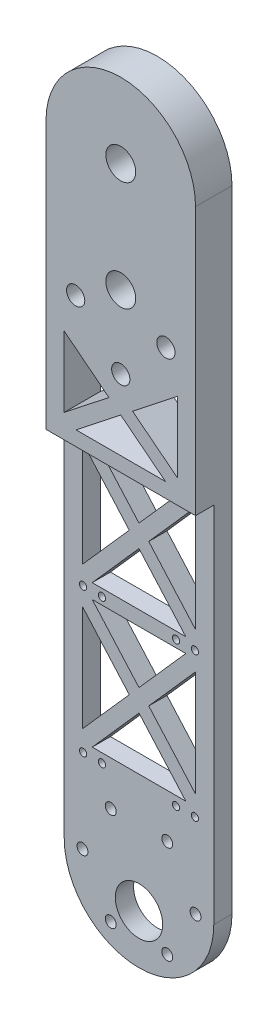
SolidWorks part; units mm, degrees
ref_plane "정면" through (0, 0, 0) normal (0, 0, 1) x (1, 0, 0)
ref_plane "윗면" through (0, 0, 0) normal (0, 1, 0) x (1, 0, 0)
ref_plane "우측면" through (0, 0, 0) normal (1, 0, 0) x (0, 0, -1)
sketch "스케치1" plane through (0, 0, 0) normal (0, 0, 1) x (1, 0, 0)
  line L0 (-20.5, 0) -> (-20.5, 173)
  line L1 (20.5, 0) -> (20.5, 173)
  line L2 (20.5, 173) -> (-20.5, 173) construction
  line L3 (-20.5, 143) -> (20.5, 143) construction
  circle A0 centre (0, 0) radius 20.5
  circle A1 centre (0, 0) radius 15.5 construction
  circle A2 centre (-15.5, 0) radius 1.5
  circle A3 centre (-7.75, 13.4234) radius 1.5
  circle A4 centre (7.75, 13.4234) radius 1.5
  circle A5 centre (15.5, 0) radius 1.5
  circle A6 centre (7.75, -13.4234) radius 1.5
  circle A7 centre (-7.75, -13.4234) radius 1.5
  circle A8 centre (0, -7) radius 6.5
  circle A9 centre (0, 173) radius 20.5
  point P19 (0, 0)
  dimension "D1" = 31
  dimension "D2" = 3
  dimension "D4" = 13
  dimension "D6" = 5
  dimension "D5" = 7
  dimension "D7" = 180
  dimension "D8" = 30
  dimension "D3" = 6
extrude "보스-돌출1" add sketch "스케치1" against normal blind 10 contours A9 L0 A0 L1 | A9 | A0 A8 A7 A6 A5 A4 A3 A2 region at (0, 86.5, 0) region at (0, 0.8114, 0) region at (0, 173, 0)
sketch "스케치2" plane through (0, 0, 0) normal (0, 0, 1) x (1, 0, 0)
  line L0 (-20.5, 143) -> (20.5, 143) construction
  circle A0 centre (0, 173) radius 4.1
  circle A1 centre (0, 143) radius 4.1
  dimension "D1" = 8.2
  dimension "D2" = 8.2
extrude "컷-돌출1" cut sketch "스케치2" against normal blind 10
sketch "스케치3" plane through (0, 0, 0) normal (0, 0, 1) x (1, 0, 0)
  line L0 (-20.5, 133) -> (20.5, 133) construction
  line L1 (-20.5, 0) -> (-20.5, 173) construction
  line L2 (20.5, 0) -> (20.5, 173) construction
  line L3 (-15.5, 128) -> (15.5, 103.625) construction
  line L4 (-20.5, 143) -> (20.5, 143) construction
  line L5 (-20.5, 20.5) -> (20.5, 20.5) construction
  line L6 (-15.5, 128) -> (15.5, 128)
  line L7 (-15.5, 128) -> (-15.5, 25.5)
  line L8 (-15.5, 25.5) -> (15.5, 25.5)
  line L9 (15.5, 128) -> (15.5, 25.5)
  line L10 (-15.5, 125.4558) -> (12.2643, 103.625)
  line L11 (-12.2643, 128) -> (15.5, 106.1692)
  line L12 (15.5, 128) -> (-15.5, 103.625) construction
  line L13 (12.2643, 128) -> (-15.5, 106.1692)
  line L14 (15.5, 125.4558) -> (-12.2643, 103.625)
  line L15 (-15.5, 99.625) -> (15.5, 99.625)
  line L16 (-15.5, 62.56) -> (15.5, 62.56) construction
  line L17 (-15.5, 64.56) -> (15.5, 64.56)
  line L18 (-15.5, 60.56) -> (15.5, 60.56)
  line L19 (-15.5, 99.625) -> (15.5, 64.56) construction
  line L20 (-15.5, 64.56) -> (15.5, 99.625) construction
  line L21 (15.5, 60.56) -> (-15.5, 25.5) construction
  line L22 (-15.5, 60.56) -> (15.5, 25.5) construction
  line L23 (-12.8305, 99.625) -> (15.5, 67.5796)
  line L24 (15.5, 103.625) -> (-15.5, 103.625)
  line L25 (-15.5, 96.6054) -> (12.8305, 64.56)
  line L26 (12.8305, 99.625) -> (-15.5, 67.5796)
  line L27 (15.5, 96.6054) -> (-12.8305, 64.56)
  line L28 (-12.8303, 60.56) -> (15.5, 28.5193)
  line L29 (-15.5, 57.5407) -> (12.8303, 25.5)
  line L30 (12.8303, 60.56) -> (-15.5, 28.5193)
  line L31 (15.5, 57.5407) -> (-12.8303, 25.5)
  circle A0 centre (0, 0) radius 20.5 construction
  point P6 (0, 71.75)
  dimension "D1" = 10
  dimension "D2" = 5
  dimension "D3" = 5
  dimension "D4" = 5
  dimension "D5" = 5
  dimension "D6" = 20.5
  dimension "D7" = 24.375
  dimension "D8" = 2
  dimension "D9" = 2
  dimension "D10" = 2
  dimension "D11" = 2
  dimension "D12" = 4
  dimension "D13" = 37.065
  dimension "D14" = 2
  dimension "D15" = 2
  dimension "D16" = 2
  dimension "D17" = 2
  dimension "D18" = 2
  dimension "D19" = 2
  dimension "D20" = 2
  dimension "D21" = 2
  dimension "D22" = 2
  dimension "D23" = 2
sketch "스케치4" plane through (0, 0, 0) normal (0, 0, 1) x (1, 0, 0)
  line L7 (-20.5, 0) -> (-20.5, 173) construction
  line L8 (20.5, -20.5) -> (-20.5, -20.5)
  line L9 (20.5, -20.5) -> (20.5, 99.625)
  line L10 (20.5, 99.625) -> (-20.5, 99.625)
  line L11 (-20.5, -20.5) -> (-20.5, 99.625)
  line L12 (-15.5, 99.625) -> (15.5, 99.625) construction
  dimension "D1" = 0
extrude "컷-돌출3" cut sketch "스케치4" against normal blind 5
extrude "컷-돌출4" cut sketch "스케치3" against normal blind 10 and the other way through all contours L9 L14 L11 | L24 L10 L14 | L13 L10 L7 region at (-11.4119, 115.8125, 0) region at (11.4119, 115.8125, 0) region at (0, 106.8394, 0)
extrude "컷-돌출5" cut sketch "스케치3<4>" against normal blind 10 and the other way through all contours L26 L15 L23 | L9 L27 L23 | L25 L27 L17 | L26 L25 L7 | L30 L18 L28 | L30 L29 L7 | L29 L31 L8 | L9 L31 L28 region at (-11.2232, 82.0925, 0) region at (0, 94.7874, 0) region at (11.2232, 82.0925, 0) region at (0, 69.3976, 0) region at (-11.2232, 43.03, 0) region at (0, 55.7231, 0) region at (11.2232, 43.03, 0) region at (0, 30.3369, 0)
sketch "스케치3<4>" plane through (0, 0, 0) normal (0, 0, 1) x (1, 0, 0) same geometry as "스케치3"
sketch "스케치5" plane through (0, 0, -5) normal (0, 0, 1) x (1, 0, 0)
  line L0 (-20.5, 99.625) -> (-20.5, 0) construction
  line L1 (20.5, 0) -> (20.5, 99.625) construction
  line L2 (-20.5, 20.5) -> (20.5, 20.5) construction
  line L3 (-15.5, 62.56) -> (15.5, 62.56) construction
  circle A0 centre (-15.33, 23) radius 1
  circle A1 centre (-10.16, 23) radius 1
  circle A2 centre (10.16, 23) radius 1
  circle A3 centre (15.33, 23) radius 1
  circle A4 centre (-15.33, 62.56) radius 1
  circle A5 centre (-10.16, 62.56) radius 1
  circle A6 centre (10.16, 62.56) radius 1
  circle A7 centre (15.33, 62.56) radius 1
  dimension "D1" = 2
  dimension "D2" = 2
  dimension "D3" = 2
  dimension "D4" = 2
  dimension "D13" = 2
  dimension "D14" = 2
  dimension "D15" = 2
  dimension "D16" = 2
  dimension "D5" = 5.17
  dimension "D6" = 5.17
  dimension "D7" = 5.17
  dimension "D8" = 5.17
  dimension "D9" = 2.5
  dimension "D10" = 2.5
  dimension "D11" = 2.5
  dimension "D12" = 2.5
  dimension "D17" = 5.17
  dimension "D18" = 5.17
  dimension "D19" = 5.17
  dimension "D20" = 5.17
extrude "컷-돌출6" cut sketch "스케치5" against normal through all
sketch "스케치6" plane through (0, 0, 0) normal (0, 0, 1) x (1, 0, 0)
  line L0 (-20.5, 143) -> (20.5, 143) construction
  line L1 (-20.5, 99.625) -> (-20.5, 173) construction
  line L2 (20.5, 0) -> (20.5, 173) construction
  circle A0 centre (-12.37, 135.5) radius 2.5
  circle A1 centre (12.375, 135.5) radius 2.5
  circle A2 centre (0, 123) radius 2.5
  circle A3 centre (0, 143) radius 4.1 construction
  dimension "D1" = 8.125
  dimension "D2" = 5
  dimension "D4" = 5
  dimension "D5" = 5
  dimension "D3" = 7.5
  dimension "D6" = 8.13
  dimension "D7" = 7.5
  dimension "D8" = 20
extrude "컷-돌출7" cut sketch "스케치6" against normal blind 10
sketch "스케치7" plane through (0, 0, 0) normal (0, 0, 1) x (1, 0, 0)
  circle A0 centre (0, 173) radius 5
  circle A1 centre (0, 143) radius 5
  dimension "D1" = 10
  dimension "D2" = 10
extrude "컷-돌출8" cut sketch "스케치7" along normal blind 1.8 from surface starting at face at (14.875, 135.5, -10)
fillet "필렛1" radius 0.2 4 edges at (4.1, 143, -8.2) (4.1, 173, -8.2) (5, 173, -10) (5, 143, -10)
